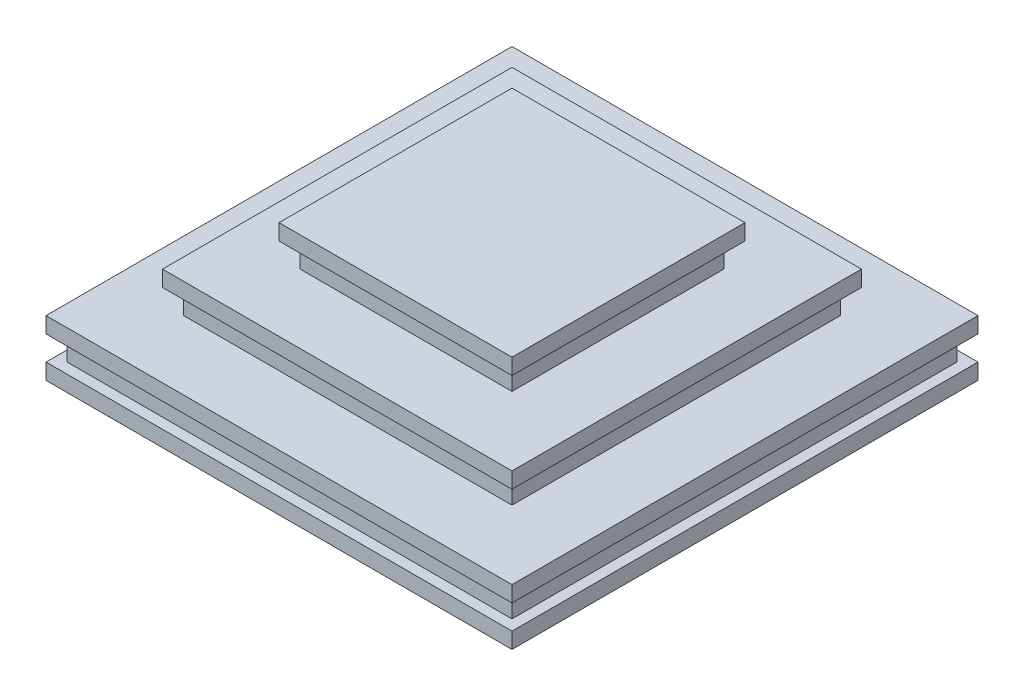
SolidWorks part; units mm, degrees
ref_plane "Front Plane" through (0, 0, 0) normal (0, 0, 1) x (1, 0, 0)
ref_plane "Top Plane" through (0, 0, 0) normal (0, 1, 0) x (1, 0, 0)
ref_plane "Right Plane" through (0, 0, 0) normal (1, 0, 0) x (0, 0, -1)
sketch "Sketch1" plane through (0, 0, 0) normal (0, 1, 0) x (1, 0, 0)
  line L0 (0, 0) -> (0, 22) construction
  line L1 (-22, 22) -> (22, 22)
  line L2 (-22, 22) -> (-22, -22)
  line L3 (-22, -22) -> (22, -22)
  line L4 (22, 22) -> (22, -22)
  line L5 (0, 0) -> (22, 0) construction
  line L6 (-21, 21) -> (21, 21)
  line L7 (21, 21) -> (21, -21)
  line L8 (-21, -21) -> (21, -21)
  line L9 (-21, 21) -> (-21, -21)
  line L10 (10, 10) -> (10, -10)
  line L11 (-11, 11) -> (11, 11)
  line L12 (-11, 11) -> (-11, -11)
  line L13 (-11, -11) -> (11, -11)
  line L14 (11, 11) -> (11, -11)
  line L15 (-10, -10) -> (10, -10)
  line L16 (-10, 10) -> (-10, -10)
  line L17 (-10, 10) -> (10, 10)
  line L18 (-22, 0) -> (-16.5, 0) construction
  line L19 (-16.5, 16.5) -> (16.5, 16.5)
  line L20 (-16.5, 16.5) -> (-16.5, -16.5)
  line L21 (-16.5, -16.5) -> (16.5, -16.5)
  line L22 (16.5, 16.5) -> (16.5, -16.5)
  line L23 (-16.5, 0) -> (-11, 0) construction
  line L24 (0, -22) -> (0, -16.5) construction
  line L25 (0, -16.5) -> (0, -10) construction
  line L26 (-15.5, -15.5) -> (15.5, -15.5)
  line L27 (15.5, 15.5) -> (15.5, -15.5)
  line L28 (-15.5, 15.5) -> (15.5, 15.5)
  line L29 (-15.5, 15.5) -> (-15.5, -15.5)
  dimension "D1" = 44
  dimension "D2" = 44
  dimension "D4" = 22
  dimension "D3" = 1
  dimension "D5" = 1
  dimension "D6" = 1
sketch "Sketch2" plane through (0, 0, 0) normal (0, 0, 1) x (1, 0, 0)
  line L0 (0, 0) -> (0, 1.5)
  line L1 (-22, 0) -> (22, 0) construction
  line L2 (0, 1.5) -> (0, 3.8)
  line L3 (0, 3.8) -> (0, 5.3)
  line L4 (0, 5.3) -> (0, 7.6)
  line L5 (0, 7.6) -> (0, 9.1)
  line L6 (0, 9.1) -> (0, 11.4)
  line L7 (0, 11.4) -> (0, 12.9)
  point P4 (0, 0)
  point P12 (0, 0)
  point P13 (0, 0)
  point P14 (0, 0)
  point P15 (0, 0)
  point P16 (0, 0)
  point P17 (0, 0)
  point P18 (0, 0)
  point P19 (0, 0)
  point P20 (0, 0)
  point P21 (0, 0)
  point P22 (0, 0)
  point P23 (0, 0)
  point P24 (0, 0)
  point P25 (0, 0)
  point P26 (0, 0)
  point P27 (0, 0)
  point P28 (0, 0)
  point P29 (0, 0)
  point P30 (0, 0)
  point P31 (0, 0)
  point P32 (0, 0)
  point P33 (0, 11.4)
  point P34 (0, 9.1)
  point P35 (0, 0)
  point P36 (0, 0)
  point P37 (0, 0)
  point P38 (0, 0)
  point P39 (0, 0)
  point P40 (0, 0)
  point P41 (0, 0)
  point P42 (0, 0)
  point P43 (0, 0)
  dimension "D1" = 12.9
  dimension "D2" = 1.5
extrude "Boss-Extrude1" add sketch "Sketch1" along normal up to vertex (1.5 mm away) contours L2 L3 L4 L1 up to point (0, 1.5, 0)
extrude "Boss-Extrude2" add sketch "Sketch1<3>" along normal up to vertex (3.8 mm away) contours L9 L8 L7 L6 up to point (0, 3.8, 0)
sketch "Sketch1<3>" plane through (0, 0, 0) normal (0, 1, 0) x (1, 0, 0) same geometry as "Sketch1"
extrude "Boss-Extrude3" add sketch "Sketch1<5>" along normal up to vertex (5.3 mm away) from vertex contours L2 L3 L4 L1 up to point (0, 5.3, 0) starting at point (0, 3.8, 0)
sketch "Sketch1<5>" plane through (0, 0, 0) normal (0, 1, 0) x (1, 0, 0) same geometry as "Sketch1"
extrude "Boss-Extrude4" add sketch "Sketch1<6>" along normal up to vertex (7.6 mm away) from vertex contours L29 L26 L27 L28 up to point (0, 7.6, 0) starting at point (0, 5.3, 0)
sketch "Sketch1<6>" plane through (0, 0, 0) normal (0, 1, 0) x (1, 0, 0) same geometry as "Sketch1"
extrude "Boss-Extrude5" add sketch "Sketch1<7>" along normal up to vertex (9.1 mm away) from vertex contours L20 L21 L22 L19 up to point (0, 9.1, 0) starting at point (0, 7.6, 0)
sketch "Sketch1<7>" plane through (0, 0, 0) normal (0, 1, 0) x (1, 0, 0) same geometry as "Sketch1"
extrude "Boss-Extrude6" add sketch "Sketch1<8>" along normal up to vertex (11.4 mm away) from vertex contours L16 L15 L10 L17 up to point (0, 11.4, 0) starting at point (0, 9.1, 0)
sketch "Sketch1<8>" plane through (0, 0, 0) normal (0, 1, 0) x (1, 0, 0) same geometry as "Sketch1"
extrude "Boss-Extrude7" add sketch "Sketch1<12>" against normal up to vertex (-11.4 mm away) from vertex contours L13 L14 L11 L12 up to point (0, 11.4, 0) starting at point (0, 12.9, 0)
sketch "Sketch1<12>" plane through (0, 0, 0) normal (0, 1, 0) x (1, 0, 0) same geometry as "Sketch1"
